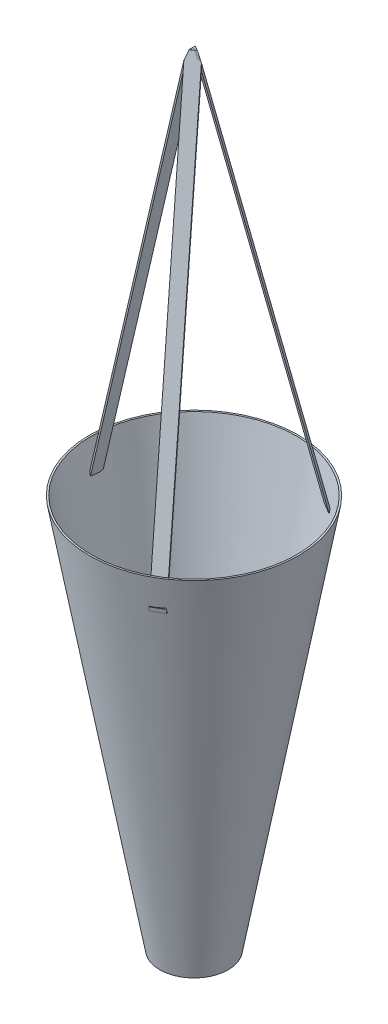
SolidWorks part; units mm, degrees
ref_plane "Front Plane" through (0, 0, 0) normal (0, 0, 1) x (1, 0, 0)
ref_plane "Top Plane" through (0, 0, 0) normal (0, 1, 0) x (1, 0, 0)
ref_plane "Right Plane" through (0, 0, 0) normal (1, 0, 0) x (0, 0, -1)
sketch "Sketch1" plane through (0, 0, 0) normal (0, 0, 1) x (1, 0, 0)
  line L0 (-152.4, 0) -> (-154.94, 0)
  line L1 (-154.94, 0) -> (-50.8, -584.2)
  line L2 (-50.8, -584.2) -> (-48.26, -584.2)
  line L3 (-48.26, -584.2) -> (-152.4, 0)
  line L4 (0, 0) -> (0, -50000) construction
  dimension "D1" = 2.54
  dimension "D2" = 2.54
  dimension "D3" = 584.2
  dimension "D4" = 152.4
  dimension "D5" = 48.26
revolve "Revolve1" add sketch "Sketch1" angle 360 about L4
sketch "Sketch2" plane through (0, 0, 0) normal (0, 0, 1) x (1, 0, 0)
  line L0 (-147.0163, -44.45) -> (-2.54, 573.8959)
  line L1 (-154.94, 0) -> (-50.8, -584.2) construction
  line L2 (0, 157.4288) -> (0, 475.3865) construction
  line L3 (-2.54, 573.8959) -> (0, 573.8959)
  line L4 (0, 573.8959) -> (-145.9171, -50.6164)
  line L5 (-145.9171, -50.6164) -> (-147.0163, -44.45)
  point P10 (-144.4763, -44.45)
  dimension "D1" = 2.54
  dimension "D2" = 2.54
  dimension "D3" = 635
  dimension "D4" = 44.45
extrude "Boss-Extrude1" add sketch "Sketch2" along normal blind 9.525 and the other way blind 9.525 separate body
pattern_circular "CirPattern2" count 3 over 360 about axis through (0, 0, 0) along (0, 1, 0) of bodies 102
sketch "Sketch3" plane through (64.7789, 30.2711, -112.2003) normal (0.4869, 0.2275, -0.8433) x (-0.8735, 0.1268, -0.4701)
  line L0 (63.2652, 554.7518) -> (60.5779, 534.2937)
  line L1 (63.2652, 554.7518) -> (82.142, 552.2722)
  line L2 (60.5779, 534.2937) -> (79.4546, 531.8141)
  line L3 (82.142, 552.2722) -> (79.4546, 531.8141)
  line L4 (63.2652, 554.7518) -> (-19.4377, -74.8395) construction
extrude "Cut-Extrude2" cut sketch "Sketch3" along normal blind 9.525
sketch "Sketch4" plane through (64.7789, 30.2711, 112.2003) normal (0.4869, 0.2275, 0.8433) x (0.8735, -0.1268, -0.4701)
  line L0 (-82.153, 552.2707) -> (-79.6955, 533.5625)
  line L1 (-82.153, 552.2707) -> (-63.166, 554.7649)
  line L2 (-79.6955, 533.5625) -> (-60.7085, 536.0567)
  line L3 (-63.166, 554.7649) -> (-60.7085, 536.0567)
  line L4 (-82.153, 552.2707) -> (0.55, -77.3206) construction
extrude "Cut-Extrude3" cut sketch "Sketch4" along normal blind 9.525
sketch "Sketch5" plane through (-129.5577, 30.2711, 0) normal (-0.9738, 0.2275, 0) x (0, 0, 1)
  line L0 (-9.525, 538.4393) -> (-9.525, 559.7926)
  line L1 (-9.525, 538.4393) -> (9.6437, 538.4393)
  line L2 (-9.525, 559.7926) -> (9.6437, 559.7926)
  line L3 (9.6437, 538.4393) -> (9.6437, 559.7926)
  line L4 (-9.525, 545.316) -> (-9.525, -76.7336) construction
extrude "Cut-Extrude4" cut sketch "Sketch5" along normal blind 9.525
